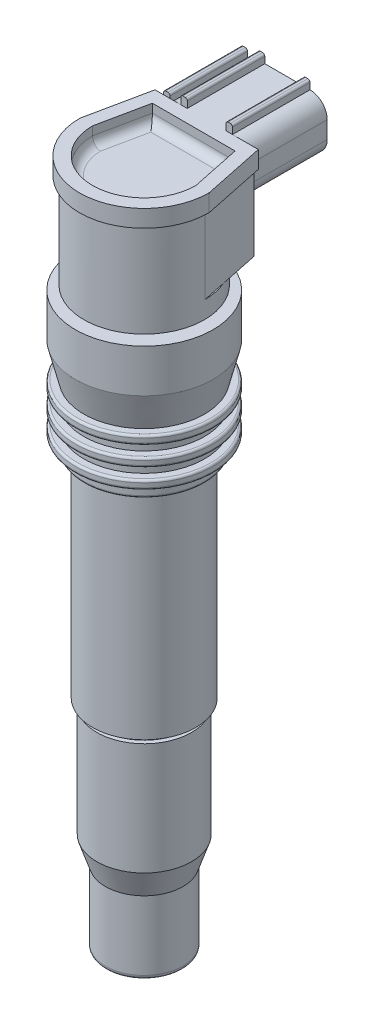
SolidWorks part; units mm, degrees
ref_plane "Front Plane" through (0, 0, 0) normal (0, 0, 1) x (1, 0, 0)
ref_plane "Top Plane" through (0, 0, 0) normal (0, 1, 0) x (1, 0, 0)
ref_plane "Right Plane" through (0, 0, 0) normal (1, 0, 0) x (0, 0, -1)
sketch "Sketch1" plane through (0, 0, 0) normal (0, 0, 1) x (1, 0, 0)
  line L0 (0, 8.89) -> (1.769, 8.89)
  line L1 (1.769, 8.89) -> (3.9688, 10.16)
  line L2 (3.9688, 10.16) -> (3.9688, -7.6237)
  line L3 (4.7625, -8.4175) -> (6.35, -8.4175)
  line L4 (7.1438, -7.6237) -> (7.1438, 5.0763)
  line L5 (7.1438, 5.0763) -> (8.7313, 9.8388)
  line L6 (8.7313, 9.8388) -> (8.7313, 30.4763)
  line L7 (8.7313, 30.4763) -> (7.9375, 30.4763)
  line L8 (7.9375, 30.4763) -> (8.7313, 31.6669)
  line L9 (8.7313, 31.6669) -> (9.525, 31.6669)
  line L10 (9.525, 31.6669) -> (9.525, 71.3544)
  line L11 (9.525, 71.3544) -> (10.7156, 71.3544)
  line L12 (11.1125, 71.7513) -> (11.1125, 73.7357)
  line L13 (11.1125, 73.7357) -> (12.3031, 73.7357)
  line L14 (12.7, 74.1325) -> (12.7, 74.9263)
  line L15 (12.3031, 75.3232) -> (11.1125, 75.3232)
  line L16 (11.1125, 75.3232) -> (11.1125, 77.3075)
  line L17 (11.1125, 77.3075) -> (12.3031, 77.3075)
  line L18 (12.7, 77.7044) -> (12.7, 78.4982)
  line L19 (12.3031, 78.895) -> (11.1125, 78.895)
  line L20 (11.1125, 78.895) -> (11.1125, 80.8794)
  line L21 (11.1125, 80.8794) -> (12.3031, 80.8794)
  line L22 (12.7, 81.2763) -> (12.7, 82.07)
  line L23 (12.3031, 82.4669) -> (11.1125, 82.4669)
  line L24 (11.1125, 82.4669) -> (12.7, 88.8169)
  line L25 (12.7, 88.8169) -> (12.7, 96.7544)
  line L26 (12.7, 96.7544) -> (9.525, 96.7544)
  line L27 (9.525, 96.7544) -> (9.525, 97.5482)
  line L28 (9.525, 97.5482) -> (11.1125, 97.5482)
  line L29 (11.1125, 97.5482) -> (11.1125, 100.7232)
  line L30 (11.1125, 100.7232) -> (0, 100.7232)
  line L31 (0, -41.4558) -> (0, 127.9124) construction
  line L32 (0, 8.89) -> (0, 100.7232)
  arc A0 (3.9688, -7.6237) -> (4.7625, -8.4175) centre (4.7625, -7.6237) ccw
  arc A1 (6.35, -8.4175) -> (7.1438, -7.6237) centre (6.35, -7.6237) ccw
  arc A2 (10.7156, 71.3544) -> (11.1125, 71.7513) centre (10.7156, 71.7513) ccw
  arc A3 (12.3031, 73.7357) -> (12.7, 74.1325) centre (12.3031, 74.1325) ccw
  arc A4 (12.7, 74.9263) -> (12.3031, 75.3232) centre (12.3031, 74.9263) ccw
  arc A5 (12.3031, 77.3075) -> (12.7, 77.7044) centre (12.3031, 77.7044) ccw
  arc A6 (12.7, 78.4982) -> (12.3031, 78.895) centre (12.3031, 78.4982) ccw
  arc A7 (12.3031, 80.8794) -> (12.7, 81.2763) centre (12.3031, 81.2763) ccw
  arc A8 (12.7, 82.07) -> (12.3031, 82.4669) centre (12.3031, 82.07) ccw
  point P37 (3.9688, -8.4175)
  point P40 (7.1438, -8.4175)
  point P43 (11.1125, 71.3544)
  point P46 (12.7, 73.7357)
  point P49 (12.7, 75.3232)
  point P52 (12.7, 77.3075)
  point P55 (12.7, 78.895)
  point P58 (12.7, 80.8794)
  point P61 (12.7, 82.4669)
  dimension "D35" = 0.7937
  dimension "D36" = 0.3969
  dimension "D1" = 11.1125
  dimension "D2" = 3.175
  dimension "D3" = 1.5875
  dimension "D4" = 0.7937
  dimension "D5" = 3.175
  dimension "D6" = 7.9375
  dimension "D7" = 6.35
  dimension "D8" = 1.5875
  dimension "D9" = 1.5875
  dimension "D10" = 8.7313
  dimension "D12" = 1.5875
  dimension "D13" = 1.5875
  dimension "D14" = 1.5875
  dimension "D15" = 1.5875
  dimension "D17" = 1.5875
  dimension "D18" = 1.5875
  dimension "D19" = 1.5875
  dimension "D20" = 11.1125
  dimension "D21" = 1.5875
  dimension "D22" = 39.6875
  dimension "D23" = 0.7937
  dimension "D24" = 0.7937
  dimension "D25" = 0.7937
  dimension "D26" = 1.1906
  dimension "D27" = 20.6375
  dimension "D28" = 4.7625
  dimension "D29" = 1.5875
  dimension "D30" = 13.4937
  dimension "D31" = 3.175
  dimension "D32" = 10.16
  dimension "D33" = 8.89
  dimension "D34" = 60
  dimension "D37" = 100.7232
revolve "Revolve1" add sketch "Sketch1" angle 360 about L31
sketch "Sketch2" plane through (0, 100.7232, 0) normal (0, 1, 0) x (-1, 0, 0)
  line L0 (8.7313, -11.5094) -> (-8.7312, -11.5094)
  line L1 (11.1122, -0.0794) -> (8.7313, -11.5094)
  line L2 (-8.7312, -11.5094) -> (-11.1122, -0.0794)
  arc A0 (-11.1122, -0.0794) -> (11.1122, -0.0794) centre (0, 0) cw
  dimension "D2" = 11.1125
  dimension "D1" = 11.5094
  dimension "D3" = 17.4625
  dimension "D4" = 8.7312
  dimension "D5" = 11.43
  dimension "D6" = 11.43
extrude "Extrude1" add sketch "Sketch2" along normal blind 14.2875
sketch "Sketch3" plane through (0, 115.0107, 0) normal (0, 1, 0) x (-1, 0, 0)
  line L0 (9.525, -11.5094) -> (-9.525, -11.5094)
  line L2 (11.906, -0.0793) -> (9.525, -11.5094)
  line L3 (-11.906, -0.0793) -> (-9.525, -11.5094)
  line L4 (8.7313, -11.5094) -> (11.1122, -0.0794) construction
  line L5 (-11.1122, -0.0794) -> (-8.7312, -11.5094) construction
  arc A0 (-11.906, -0.0793) -> (11.906, -0.0793) centre (0, 0) cw
  arc A1 (11.1122, -0.0794) -> (-11.1122, -0.0794) centre (0, 0) ccw construction
  dimension "D1" = 0.7937
  dimension "D2" = 19.05
  dimension "D3" = 9.525
extrude "Extrude2" add sketch "Sketch3" along normal blind 3.175
sketch "Sketch4" plane through (0, 118.1857, 0) normal (0, 1, 0) x (-1, 0, 0)
  line L0 (9.525, 0) -> (7.6235, -9.1281)
  line L1 (7.6235, -9.1281) -> (-7.6235, -9.1281)
  line L2 (-7.6235, -9.1281) -> (-9.525, 0)
  line L3 (9.525, -11.5094) -> (11.906, -0.0793) construction
  line L4 (-11.906, -0.0793) -> (-9.525, -11.5094) construction
  line L5 (-9.525, -11.5094) -> (9.525, -11.5094) construction
  arc A0 (-9.525, 0) -> (9.525, 0) centre (0, 0) cw
  arc A1 (11.906, -0.0793) -> (-11.906, -0.0793) centre (0, 0) ccw construction
  dimension "D1" = 2.3813
  dimension "D2" = 2.3813
extrude "Cut-Extrude1" cut sketch "Sketch4" against normal blind 3.175
fillet "Fillet1" radius 1.5875 4 edges at (-8.5743, 115.0107, -4.5641) (0, 115.0107, -9.1281) (8.5743, 115.0107, -4.5641) (0, 115.0107, 9.525)
sketch "Sketch5" plane through (0, 0, -11.5094) normal (0, 0, -1) x (-1, 0, 0)
  line L0 (-9.525, 118.1857) -> (9.525, 118.1857) construction
  line L1 (-4.7625, 118.1857) -> (4.7625, 118.1857)
  line L2 (-7.9375, 115.0107) -> (-7.9375, 111.8357)
  line L3 (-4.7625, 108.6607) -> (4.7625, 108.6607)
  line L4 (7.9375, 115.0107) -> (7.9375, 111.8357)
  line L5 (-8.7312, 115.0107) -> (-8.7312, 100.7232) construction
  arc A0 (-4.7625, 118.1857) -> (-7.9375, 115.0107) centre (-4.7625, 115.0107) ccw
  arc A1 (-7.9375, 111.8357) -> (-4.7625, 108.6607) centre (-4.7625, 111.8357) ccw
  arc A2 (4.7625, 108.6607) -> (7.9375, 111.8357) centre (4.7625, 111.8357) ccw
  arc A3 (4.7625, 118.1857) -> (7.9375, 115.0107) centre (4.7625, 115.0107) cw
  point P12 (-7.9375, 118.1857)
  dimension "D4" = 3.175
  dimension "D1" = 0.7937
  dimension "D2" = 115.0107
  dimension "D3" = 3.175
  dimension "D5" = 9.525
extrude "Extrude3" add sketch "Sketch5" along normal blind 14.2875
sketch "Sketch8" plane through (0, 0, -25.7969) normal (0, 0, -1) x (-1, 0, 0)
  line L8 (4.7625, 117.3919) -> (-4.7625, 117.3919)
  line L9 (-7.1437, 115.0107) -> (-7.1437, 111.8357)
  line L10 (-4.7625, 109.4544) -> (4.7625, 109.4544)
  line L11 (7.1438, 111.8357) -> (7.1437, 115.0107)
  line L12 (4.7625, 117.3919) -> (-4.7625, 117.3919)
  line L13 (-7.1437, 115.0107) -> (-7.1437, 111.8357)
  line L14 (-4.7625, 109.4544) -> (4.7625, 109.4544)
  line L15 (7.1438, 111.8357) -> (7.1437, 115.0107)
  arc A8 (7.1437, 115.0107) -> (4.7625, 117.3919) centre (4.7625, 115.0107) ccw
  arc A9 (-4.7625, 117.3919) -> (-7.1437, 115.0107) centre (-4.7625, 115.0107) ccw
  arc A10 (-7.1437, 111.8357) -> (-4.7625, 109.4544) centre (-4.7625, 111.8357) ccw
  arc A11 (4.7625, 109.4544) -> (7.1438, 111.8357) centre (4.7625, 111.8357) ccw
  arc A12 (7.1437, 115.0107) -> (4.7625, 117.3919) centre (4.7625, 115.0107) ccw
  arc A13 (-4.7625, 117.3919) -> (-7.1437, 115.0107) centre (-4.7625, 115.0107) ccw
  arc A14 (-7.1437, 111.8357) -> (-4.7625, 109.4544) centre (-4.7625, 111.8357) ccw
  arc A15 (4.7625, 109.4544) -> (7.1438, 111.8357) centre (4.7625, 111.8357) ccw
  dimension "D1" = 0.7937
extrude "Cut-Extrude6" cut sketch "Sketch8" against normal blind 6.35
sketch "Sketch9" plane through (0, 0, -19.4469) normal (0, 0, -1) x (-1, 0, 0)
  line L8 (4.7625, 116.5982) -> (-4.7625, 116.5982)
  line L9 (-6.35, 115.0107) -> (-6.35, 111.8357)
  line L10 (-4.7625, 110.2482) -> (4.7625, 110.2482)
  line L11 (6.35, 111.8357) -> (6.35, 115.0107)
  line L12 (4.7625, 116.5982) -> (-4.7625, 116.5982)
  line L13 (-6.35, 115.0107) -> (-6.35, 111.8357)
  line L14 (-4.7625, 110.2482) -> (4.7625, 110.2482)
  line L15 (6.35, 111.8357) -> (6.35, 115.0107)
  arc A8 (6.35, 115.0107) -> (4.7625, 116.5982) centre (4.7625, 115.0107) ccw
  arc A9 (-4.7625, 116.5982) -> (-6.35, 115.0107) centre (-4.7625, 115.0107) ccw
  arc A10 (-6.35, 111.8357) -> (-4.7625, 110.2482) centre (-4.7625, 111.8357) ccw
  arc A11 (4.7625, 110.2482) -> (6.35, 111.8357) centre (4.7625, 111.8357) ccw
  arc A12 (6.35, 115.0107) -> (4.7625, 116.5982) centre (4.7625, 115.0107) ccw
  arc A13 (-4.7625, 116.5982) -> (-6.35, 115.0107) centre (-4.7625, 115.0107) ccw
  arc A14 (-6.35, 111.8357) -> (-4.7625, 110.2482) centre (-4.7625, 111.8357) ccw
  arc A15 (4.7625, 110.2482) -> (6.35, 111.8357) centre (4.7625, 111.8357) ccw
  dimension "D1" = 0.7937
extrude "Cut-Extrude7" cut sketch "Sketch9" against normal blind 7.9375
sketch "Sketch10" plane through (0, 0, -11.5094) normal (0, 0, -1) x (-1, 0, 0)
  line L0 (0, 120.3128) -> (0, 105.4686) construction
  line L1 (-4.7625, 111.6649) -> (-1.5875, 111.6649)
  line L2 (-4.7625, 111.6649) -> (-4.7625, 112.4586)
  line L3 (-4.7625, 112.4586) -> (-1.5875, 112.4586)
  line L4 (-1.5875, 111.6649) -> (-1.5875, 112.4586)
  line L5 (1.5875, 111.6649) -> (1.5875, 112.4586)
  line L6 (4.7625, 112.4586) -> (1.5875, 112.4586)
  line L7 (4.7625, 111.6649) -> (4.7625, 112.4586)
  line L8 (4.7625, 111.6649) -> (1.5875, 111.6649)
  dimension "D1" = 1.5875
  dimension "D2" = 3.175
  dimension "D3" = 0.7937
  dimension "D4" = 111.6649
extrude "Extrude5" add sketch "Sketch10" along normal blind 9.525
chamfer "Chamfer1" distance 1.5875 angle 30 4 edges at (-4.7625, 112.0617, -21.0344) (-1.5875, 112.0617, -21.0344) (4.7625, 112.0617, -21.0344) (1.5875, 112.0617, -21.0344) first distance on face at (-4.7625, 112.0617, -16.2719) first distance on face at (-1.5875, 112.0617, -16.2719) first distance on face at (4.7625, 112.0617, -16.2719) first distance on face at (1.5875, 112.0617, -16.2719)
sketch "Sketch11" plane through (0, 0, -25.7969) normal (0, 0, -1) x (-1, 0, 0)
  line L0 (7.9375, 115.0107) -> (7.9375, 118.5825)
  line L1 (-4.7625, 118.1857) -> (-3.5719, 118.1857)
  line L2 (-4.7625, 118.1857) -> (-4.7625, 119.3763)
  line L3 (-4.3656, 119.7732) -> (-3.9687, 119.7732)
  line L4 (-3.5719, 118.1857) -> (-3.5719, 119.3763)
  line L5 (4.7625, 118.1857) -> (3.5719, 118.1857)
  line L6 (4.7625, 118.1857) -> (4.7625, 119.3763)
  line L7 (4.3656, 119.7732) -> (3.9688, 119.7732)
  line L8 (3.5719, 118.1857) -> (3.5719, 119.3763)
  line L9 (7.5406, 118.9794) -> (7.1437, 118.9794)
  line L10 (6.7469, 118.5825) -> (6.7469, 117.4891)
  arc A0 (7.9375, 115.0107) -> (4.7625, 118.1857) centre (4.7625, 115.0107) ccw construction
  arc A1 (-4.7625, 119.3763) -> (-4.3656, 119.7732) centre (-4.3656, 119.3763) cw
  arc A2 (-3.9687, 119.7732) -> (-3.5719, 119.3763) centre (-3.9687, 119.3763) cw
  arc A3 (3.9688, 119.7732) -> (3.5719, 119.3763) centre (3.9688, 119.3763) ccw
  arc A4 (4.7625, 119.3763) -> (4.3656, 119.7732) centre (4.3656, 119.3763) ccw
  arc A5 (7.1437, 118.9794) -> (6.7469, 118.5825) centre (7.1437, 118.5825) ccw
  arc A6 (7.9375, 118.5825) -> (7.5406, 118.9794) centre (7.5406, 118.5825) ccw
  arc A7 (6.7469, 117.4891) -> (7.9375, 115.0107) centre (4.7625, 115.0107) cw
  point P17 (-4.7625, 119.7732)
  point P20 (-3.5719, 119.7732)
  point P23 (3.5719, 119.7732)
  point P26 (4.7625, 119.7732)
  point P29 (6.7469, 118.9794)
  point P32 (7.9375, 118.9794)
  dimension "D7" = 0.3969
  dimension "D1" = 1.1906
  dimension "D2" = 1.1906
  dimension "D3" = 1.1906
  dimension "D4" = 1.5875
  dimension "D5" = 1.5875
  dimension "D6" = 3.9688
extrude "Extrude6" add sketch "Sketch11" against normal blind 14.2875
